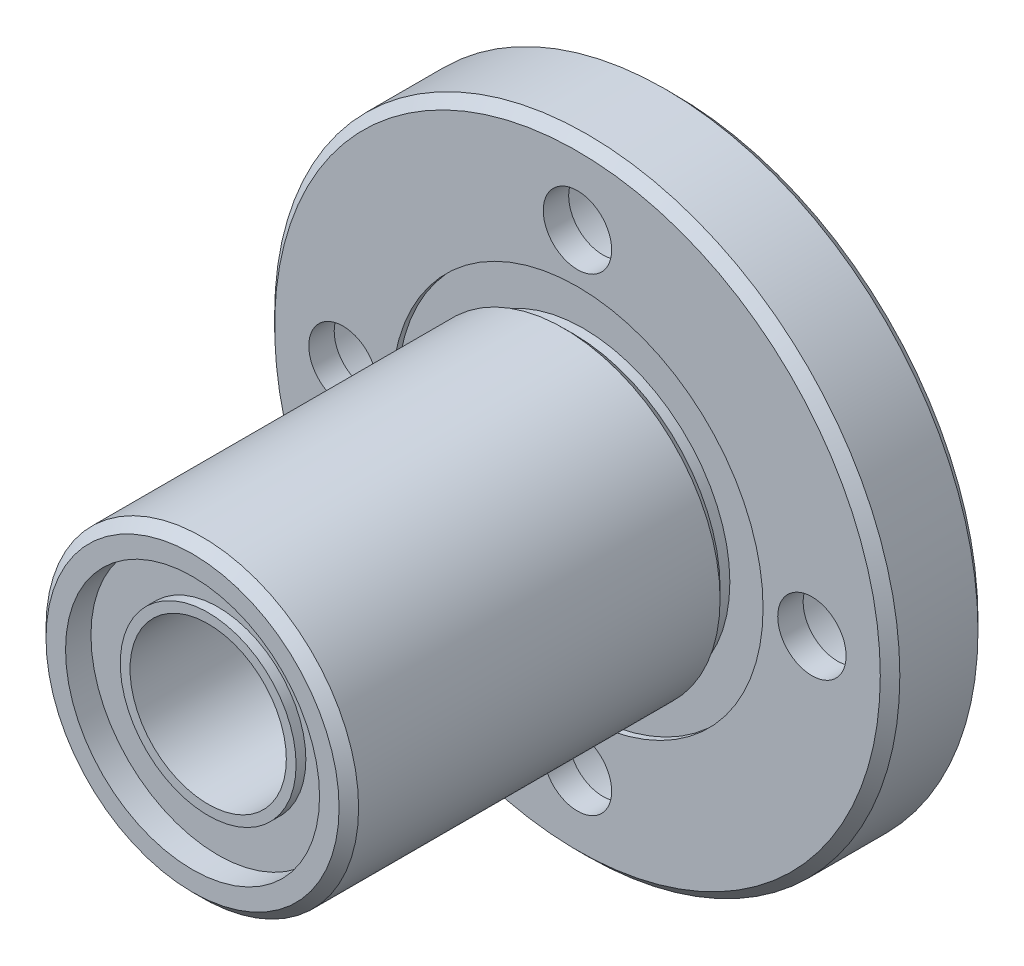
SolidWorks part; units mm, degrees
ref_plane "Ön Düzlem" through (0, 0, 0) normal (0, 0, 1) x (1, 0, 0)
ref_plane "Üst Düzlem" through (0, 0, 0) normal (0, 1, 0) x (1, 0, 0)
ref_plane "Sağ Düzlem" through (0, 0, 0) normal (1, 0, 0) x (0, 0, -1)
sketch "Çizim1" plane through (0, 0, 0) normal (0, 0, 1) x (1, 0, 0)
  circle A0 centre (0, 0) radius 16
  dimension "D1" = 32
extrude "Yükseklik-Ekstrüzyon1" add sketch "Çizim1" along normal blind 5
sketch "Çizim2" plane through (0, 0, 5) normal (0, 0, 1) x (1, 0, 0)
  circle A0 centre (0, 0) radius 8
  dimension "D1" = 16
extrude "Yükseklik-Ekstrüzyon2" add sketch "Çizim2" along normal blind 19.7
sketch "Çizim3" plane through (0, 0, 24.7) normal (0, 0, 1) x (1, 0, 0)
  circle A0 centre (0, 0) radius 4
  dimension "D1" = 8
extrude "Kes-Ekstrüzyon1" cut sketch "Çizim3" against normal up to next
sketch "Çizim4" plane through (0, 0, 0) normal (0, 0, -1) x (-1, 0, 0)
  circle A0 centre (0, 0) radius 12 construction
  circle A1 centre (-12, 0) radius 1.75
  circle A2 centre (0, 12) radius 1.75
  circle A3 centre (12, 0) radius 1.75
  circle A4 centre (0, -12) radius 1.75
  circle A5 centre (0, 12) radius 3.25
  circle A6 centre (12, 0) radius 3.25
  circle A7 centre (0, -12) radius 3.25
  circle A8 centre (-12, 0) radius 3.25
  dimension "D1" = 24
  dimension "D2" = 3.5
  dimension "D3" = 6.5
extrude "Kes-Ekstrüzyon2" cut sketch "Çizim4" against normal up to next contours A2 | A3 | A4 | A1 region at (12, 0, 0) region at (0, 12, 0) region at (-12, 0, 0) region at (0, -12, 0)
extrude "Kes-Ekstrüzyon3" cut sketch "Çizim4<3>" against normal blind 3.7
sketch "Çizim4<3>" plane through (0, 0, 0) normal (0, 0, -1) x (-1, 0, 0) same geometry as "Çizim4"
sketch "Çizim5" plane through (0, 0, 24.7) normal (0, 0, 1) x (1, 0, 0)
  circle A0 centre (0, 0) radius 6.5
  dimension "D1" = 13
extrude "Kes-Ekstrüzyon4" cut sketch "Çizim5" against normal blind 1.3
extrude "Kes-Ekstrüzyon5" cut sketch "Çizim5<2>" along normal blind 1.3 from surface starting at face at (-3.25, 12, 0)
sketch "Çizim5<2>" plane through (0, 0, 24.7) normal (0, 0, 1) x (1, 0, 0) same geometry as "Çizim5"
sketch "Çizim7" plane through (0, 0, 5) normal (0, 0, 1) x (1, 0, 0)
  circle A0 centre (0, 0) radius 9.5
  circle A1 centre (0, 0) radius 8 construction
  circle A2 centre (0, 0) radius 8
  dimension "D1" = 19
extrude "Kes-Ekstrüzyon7" cut sketch "Çizim7" against normal offset from surface (0.3 mm away) 20 up to face at (6.5, 0, 24.7)
sketch "Çizim8" plane through (0, 0, 4.7) normal (0, 0, 1) x (1, 0, 0)
  circle A0 centre (0, 0) radius 8 construction
  circle A1 centre (0, 0) radius 8
  circle A2 centre (0, 0) radius 7.5
  dimension "D1" = 0.5
extrude "Kes-Ekstrüzyon8" cut sketch "Çizim8" along normal blind 1
chamfer "Pah1" distance 0.5 angle 45 1 edges at (7.5, 0, 5.7)
sketch "Çizim9" plane through (0, 0, 23.4) normal (0, 0, 1) x (1, 0, 0)
  circle A0 centre (0, 0) radius 4 construction
  circle A1 centre (0, 0) radius 4
  circle A2 centre (0, 0) radius 4.5
  dimension "D1" = 0.5
extrude "Yükseklik-Ekstrüzyon3" add sketch "Çizim9" along normal blind 0.5
extrude "Yükseklik-Ekstrüzyon4" add sketch "Çizim9<2>" against normal blind 0.5 from surface starting at face at (6.5, 0, 1.3)
sketch "Çizim9<2>" plane through (0, 0, 23.4) normal (0, 0, 1) x (1, 0, 0) same geometry as "Çizim9"
chamfer "Pah2" distance 0.5 angle 45 3 edges at (8, 0, 24.7) (16, 0, 0) (16, 0, 5)
